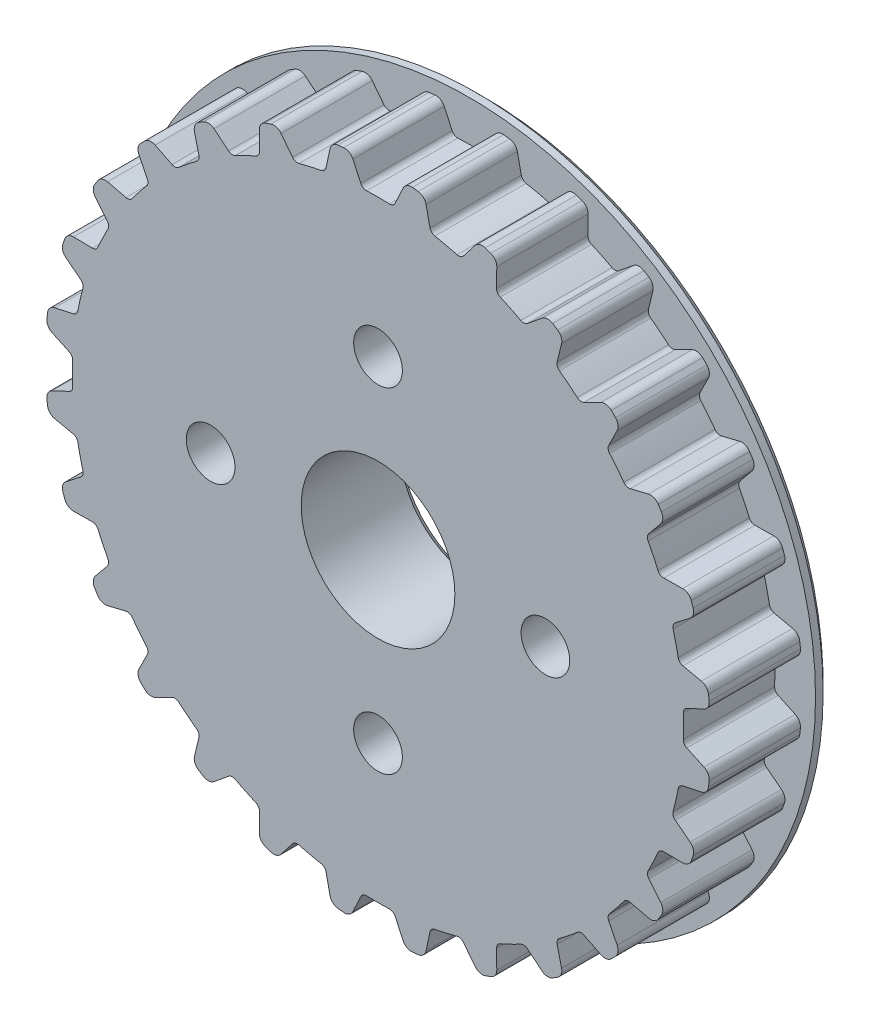
SolidWorks part; units mm, degrees
material "ABS"
ref_plane "正面" through (0, 0, 0) normal (0, 0, 1) x (1, 0, 0)
ref_plane "平面" through (0, 0, 0) normal (0, 1, 0) x (1, 0, 0)
ref_plane "右側面" through (0, 0, 0) normal (1, 0, 0) x (0, 0, -1)
sketch "ｽｹｯﾁ1" plane through (0, 0, 0) normal (0, 0, 1) x (1, 0, 0)
  line L0 (0, 0) -> (0, 20.7562) construction
  line L1 (-1.1275, 20.2917) -> (-1.6513, 21.415)
  line L2 (1.1275, 20.2917) -> (1.6513, 21.415)
  line L3 (-2.4492, 21.7375) -> (0, 0) construction
  line L4 (0, 0) -> (2.4492, 21.7375) construction
  line L5 (-2.4492, 21.7375) -> (-0.5598, 4.9686)
  line L6 (0.5598, 4.9686) -> (2.4492, 21.7375)
  arc A0 (0.75, 20.061) -> (-0.75, 20.061) centre (0, 0) ccw
  arc A1 (-0.75, 20.061) -> (-1.1275, 20.2917) centre (-0.7649, 20.4607) cw
  arc A2 (-1.6513, 21.415) -> (-2.257, 21.7583) centre (-2.1951, 21.1615) ccw
  arc A3 (-2.257, 21.7583) -> (-2.4492, 21.7375) centre (0, 0) ccw
  arc A4 (2.257, 21.7583) -> (2.4492, 21.7375) centre (0, 0) cw
  arc A5 (1.6513, 21.415) -> (2.257, 21.7583) centre (2.1951, 21.1615) cw
  arc A6 (0.75, 20.061) -> (1.1275, 20.2917) centre (0.7649, 20.4607) ccw
  arc A7 (-0.5598, 4.9686) -> (0.5598, 4.9686) centre (0, 0) ccw
  dimension "D2" = 0.4
  dimension "D3" = 21.875
  dimension "D4" = 0.6
  dimension "D5" = 1.8
  dimension "D8" = 5
  dimension "D1" = 25
  dimension "D6" = 1.5
  dimension "D7" = 12.857
extrude "ﾎﾞｽ - 押し出し1" add sketch "ｽｹｯﾁ1" along normal blind 6
pattern_circular "円形ﾊﾟﾀｰﾝ1" count 28 over 360 about axis through (0, 0, 6) along (0, 0, -1) of "ﾎﾞｽ - 押し出し1"
sketch "ｽｹｯﾁ4" plane through (0, 0, 0) normal (0, 0, -1) x (-1, 0, 0)
  circle A0 centre (0, 0) radius 22.75
  dimension "D1" = 45.5
extrude "ﾎﾞｽ - 押し出し2" add sketch "ｽｹｯﾁ4" along normal blind 1
sketch "ｽｹｯﾁ2" plane through (0, 0, 6) normal (0, 0, 1) x (1, 0, 0)
  circle A0 centre (0, 0) radius 5.05
  dimension "D1" = 10.1
extrude "ｶｯﾄ - 押し出し1" cut sketch "ｽｹｯﾁ2" against normal through all
sketch "ｽｹｯﾁ3" plane through (0, 0, 6) normal (0, 0, 1) x (1, 0, 0)
  line L0 (0, 11) -> (0, 0) construction
  line L1 (11, 0) -> (0, 0) construction
  line L2 (0, -11) -> (0, 0) construction
  line L3 (-11, 0) -> (0, 0) construction
  circle A0 centre (0, 11) radius 1.6
  circle A1 centre (11, 0) radius 1.6
  circle A2 centre (0, -11) radius 1.6
  circle A3 centre (-11, 0) radius 1.6
  point P12 (0, 0)
  dimension "D1" = 3.2
  dimension "D2" = 11
  dimension "D3" = 4
extrude "ｶｯﾄ - 押し出し2" cut sketch "ｽｹｯﾁ3" against normal through all
chamfer "面取り1" distance 2 angle 45 4 edges at (-9.4, 0, -1) (1.6, 11, -1) (1.6, -11, -1) (12.6, 0, -1)
chamfer "面取り2" distance 0.5 angle 45 2 edges at (5.05, 0, -1) (-22.75, 0, -1)
